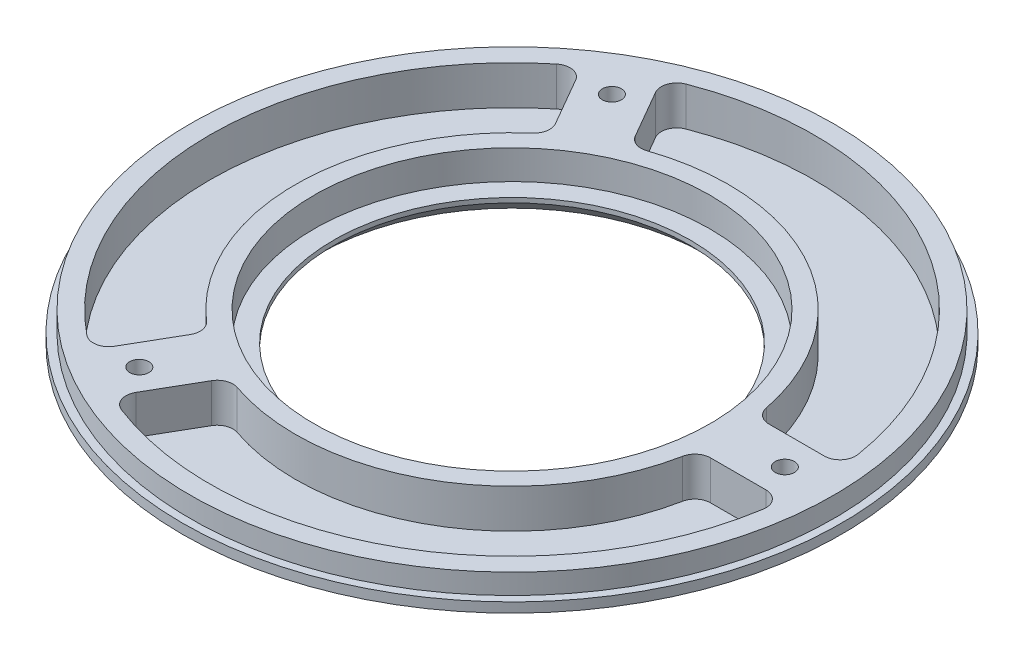
SolidWorks part; units mm, degrees
material "6061-T6 (SS)"
ref_plane "Front Plane" through (0, 0, 0) normal (0, 0, 1) x (1, 0, 0)
ref_plane "Top Plane" through (0, 0, 0) normal (0, 1, 0) x (1, 0, 0)
ref_plane "Right Plane" through (0, 0, 0) normal (1, 0, 0) x (0, 0, -1)
sketch "Sketch2" plane through (0, 0, 0) normal (1, 0, 0) x (0, 0, -1)
  line L0 (-45.8, 0) -> (-82.55, 0)
  line L1 (-82.55, 0) -> (-82.55, 12.7)
  line L2 (-82.55, 12.7) -> (-50.8, 12.7)
  line L3 (-45.8, 0) -> (-45.8, 5.2)
  line L4 (-45.8, 5.2) -> (-50.8, 5.2)
  line L5 (-50.8, 5.2) -> (-50.8, 12.7)
  line L6 (-80.2166, 12.7) -> (-80.2166, 0) construction
  dimension "D1" = 82.55
  dimension "D2" = 12.7
  dimension "D3" = 50.8
  dimension "D4" = 5
  dimension "D5" = 7.5
ref_axis "Axis1" through (0, -0.9004, 0) along (0, 1, 0)
revolve "Revolve1" add sketch "Sketch2" angle 360 about axis through (0, -0.9004, 0) along (0, 1, 0)
hole_wizard "#90 (0.0087) Diameter Hole1" positions "Sketch6" profile "Sketch7" hole size "#90" standard "ANSI Inch" end condition through all
sketch "Sketch6" plane through (0, 12.7, 0) normal (0, 1, 0) x (1, 0, 0)
  line L0 (0, 0) -> (-69.8201, 120.932) construction
  line L2 (0, 0) -> (0, 109.0908) construction
  point P0 (-35, 60.6218)
  dimension "D1" = 30
  dimension "D2" = 70
sketch "Sketch7" plane through (-35, 12.7, -60.6218) normal (1, 0, 0) x (0, 0, 1)
  line L0 (0, 0) -> (0, 12.7)
  line L1 (0, 12.7) -> (0.1105, 12.7)
  line L2 (0.1105, 12.7) -> (0.1105, 0)
  line L5 (0.1105, 0) -> (0, 0)
  line L11 (0, -6.35) -> (0, 107.95) construction
  dimension "Thru Hole Dia." = 0.221
  dimension "Thru Hole Depth" = 12.7
pattern_circular "CirPattern3" count 3 over 360 about axis through (0, -0.9004, 0) along (0, 1, 0) of "#90 (0.0087) Diameter Hole1"
sketch "Sketch8" plane through (0, 12.7, 0) normal (0, 1, 0) x (1, 0, 0)
  line L4 (0, 0) -> (46.9997, 81.4059) construction
  line L5 (-21.0255, 51.4172) -> (-32.098, 70.5955)
  line L6 (55.0414, 7.5) -> (77.1865, 7.5)
  line L7 (0, 0) -> (-35, 60.6218) construction
  arc A0 (-21.0255, 51.4172) -> (55.0414, 7.5) centre (0, 0) cw
  arc A1 (-32.098, 70.5955) -> (77.1865, 7.5) centre (0, 0) cw
  circle A2 centre (0, 0) radius 82.55 construction
  dimension "D1" = 27
  dimension "D2" = 5
  dimension "D3" = 7.5
  dimension "D4" = 60
extrude "Cut-Extrude1" cut sketch "Sketch8" against normal blind 10
fillet "Fillet1" radius 4 4 edges at (-21.0255, 7.7, -51.4172) (55.0414, 7.7, -7.5) (77.1865, 7.7, -7.5) (-32.098, 7.7, -70.5955)
pattern_circular "CirPattern4" count 3 over 360 about axis through (0, -0.9004, 0) along (0, 1, 0) of "Cut-Extrude1", "Fillet1"
chamfer "Chamfer1" distance 4 angle 45 1 edges at (0, 0, -45.8)
sketch "Sketch10" plane through (0, 0, 0) normal (0, -1, 0) x (1, 0, 0)
  circle A0 centre (0, 0) radius 82.55
  circle A1 centre (0, 0) radius 84.55
  circle A2 centre (0, 0) radius 82.55 construction
  dimension "D1" = 2
extrude "Boss-Extrude1" add sketch "Sketch10" against normal blind 7.5
chamfer "Chamfer3" distance 5 angle 60 1 edges at (0, 0, -84.55) first distance on face at (0, 7.5, -84.55)
fillet "Fillet4" radius 5 1 edges at (0, 0, 75.8897)
hole_wizard "CBORE for #10 Binding Head Machine Screw1" positions "Sketch13" profile "Sketch14" counterbore size "#10" standard "ANSI Inch" end condition through all
sketch "Sketch13" plane through (0, 0, 0) normal (0, -1, 0) x (-1, 0, 0)
  point P4 (35, 60.6218)
sketch "Sketch14" plane through (-35, 0, -60.6218) normal (1, 0, 0) x (0, 0, -1)
  line L0 (0, 0) -> (0, 12.7)
  line L1 (0, 12.7) -> (2.4574, 12.7)
  line L3 (2.4574, 12.7) -> (2.4575, 2.794)
  line L4 (2.4575, 2.794) -> (4.7625, 2.794)
  line L5 (4.7625, 2.794) -> (4.7625, 0)
  line L7 (4.7625, 0) -> (0, 0)
  line L11 (0, -6.35) -> (0, 107.95) construction
  dimension "Thru Hole Dia." = 4.9149
  dimension "Thru Hole Depth" = 12.7
  dimension "C'Bore Dia." = 9.525
  dimension "C'Bore Depth" = 2.794
pattern_circular "CirPattern5" count 3 over 360 about axis through (0, -0.9004, 0) along (0, 1, 0) of "CBORE for #10 Binding Head Machine Screw1"
equation "\"TubeDiameter\" = 6.500in"
